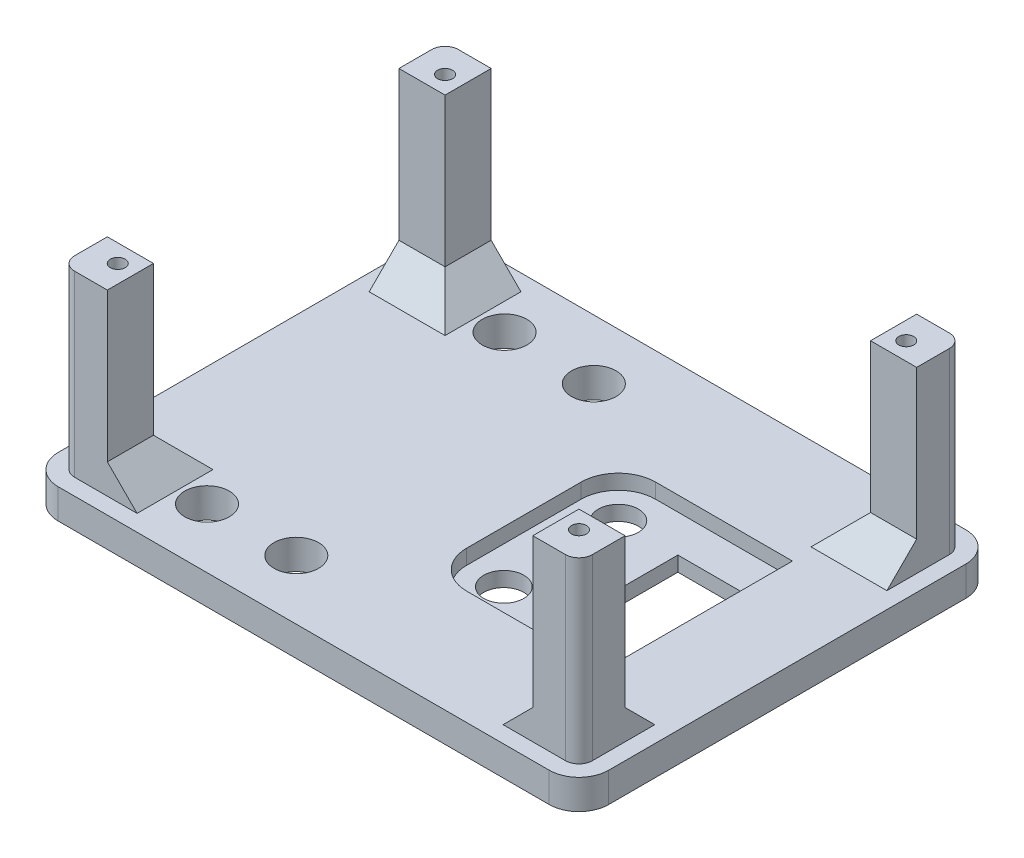
SolidWorks part; units mm, degrees
ref_plane "Front Plane" through (0, 0, 0) normal (0, 0, 1) x (1, 0, 0)
ref_plane "Top Plane" through (0, 0, 0) normal (0, 1, 0) x (1, 0, 0)
ref_plane "Right Plane" through (0, 0, 0) normal (1, 0, 0) x (0, 0, -1)
sketch "Sketch1" plane through (0, 0, 0) normal (0, 1, 0) x (1, 0, 0)
  line L1 (0, 0) -> (93.98, 0)
  line L2 (0, 0) -> (0, 71.12)
  line L3 (0, 71.12) -> (93.98, 71.12)
  line L4 (93.98, 0) -> (93.98, 71.12)
  dimension "D1" = 93.98
  dimension "D2" = 71.12
extrude "Boss-Extrude1" add sketch "Sketch1" along normal blind 5.08
sketch "Sketch2" plane through (0, 5.08, 0) normal (0, 1, 0) x (1, 0, 0)
  line L0 (46.99, 71.12) -> (46.99, 0) construction
  line L1 (2.794, 68.326) -> (10.668, 68.326)
  line L2 (2.794, 68.326) -> (2.794, 60.452)
  line L3 (2.794, 60.452) -> (10.668, 60.452)
  line L4 (10.668, 68.326) -> (10.668, 60.452)
  line L17 (93.98, 71.12) -> (0, 71.12) construction
  line L18 (0, 0) -> (93.98, 0) construction
  line L19 (0, 35.56) -> (93.98, 35.56) construction
  line L20 (0, 71.12) -> (0, 0) construction
  line L21 (93.98, 0) -> (93.98, 71.12) construction
  line L22 (83.312, 68.326) -> (83.312, 60.452)
  line L23 (91.186, 60.452) -> (83.312, 60.452)
  line L24 (91.186, 68.326) -> (91.186, 60.452)
  line L25 (91.186, 68.326) -> (83.312, 68.326)
  line L26 (91.186, 2.794) -> (83.312, 2.794)
  line L27 (91.186, 2.794) -> (91.186, 10.668)
  line L28 (91.186, 10.668) -> (83.312, 10.668)
  line L29 (83.312, 2.794) -> (83.312, 10.668)
  line L30 (10.668, 2.794) -> (10.668, 10.668)
  line L31 (2.794, 10.668) -> (10.668, 10.668)
  line L32 (2.794, 2.794) -> (2.794, 10.668)
  line L33 (2.794, 2.794) -> (10.668, 2.794)
  dimension "D1" = 7.874
  dimension "D2" = 7.874
  dimension "D3" = 2.794
  dimension "D4" = 2.794
fillet "Fillet4" radius 5.08 4 edges at (0, 2.54, -71.12) (93.98, 2.54, -71.12) (93.98, 2.54, 0) (0, 2.54, 0)
sketch "Sketch7" plane through (0, 5.08, 0) normal (0, 1, 0) x (1, 0, 0)
  line L0 (65.532, 35.56) -> (78.74, 35.56) construction
  line L1 (65.532, 45.339) -> (78.74, 45.339)
  line L2 (65.532, 45.339) -> (65.532, 25.781)
  line L3 (65.532, 25.781) -> (78.74, 25.781)
  line L4 (78.74, 45.339) -> (78.74, 25.781)
  circle A0 centre (55.372, 45.339) radius 3.429
  circle A1 centre (55.372, 25.781) radius 3.429
  dimension "D1" = 6.858
  dimension "D2" = 6.858
  dimension "D3" = 19.558
  dimension "D4" = 13.208
  dimension "D5" = 10.16
  dimension "D6" = 30.48
  dimension "D7" = 15.24
extrude "Cut-Extrude5" cut sketch "Sketch7" against normal up to next
sketch "Sketch8" plane through (0, 5.08, 0) normal (0, 1, 0) x (1, 0, 0)
  line L0 (5.08, 0) -> (88.9, 0) construction
  line L3 (0, 35.56) -> (93.98, 35.56) construction
  line L4 (0, 66.04) -> (0, 5.08) construction
  line L5 (93.98, 5.08) -> (93.98, 66.04) construction
  circle A2 centre (20.32, 10.16) radius 3.81
  circle A3 centre (35.56, 10.16) radius 3.81
  circle A4 centre (35.56, 60.96) radius 3.81
  circle A5 centre (20.32, 60.96) radius 3.81
  dimension "D1" = 15.24
  dimension "D2" = 7.62
  dimension "D4" = 7.62
  dimension "D3" = 10.16
  dimension "D5" = 15.24
sketch "Sketch9" plane through (0, 5.08, 0) normal (0, 1, 0) x (1, 0, 0)
  line L0 (55.372, 45.339) -> (55.372, 25.781) construction
  line L2 (49.022, 45.339) -> (49.022, 25.781)
  line L4 (65.532, 51.689) -> (78.74, 51.689)
  line L6 (65.532, 19.431) -> (78.74, 19.431)
  line L7 (78.74, 51.689) -> (78.74, 19.431)
  line L10 (78.74, 25.781) -> (78.74, 45.339) construction
  line L11 (55.372, 19.431) -> (65.532, 19.431)
  line L12 (55.372, 51.689) -> (65.532, 51.689)
  arc A0 (55.372, 51.689) -> (49.022, 45.339) centre (55.372, 45.339) ccw
  arc A1 (49.022, 25.781) -> (55.372, 19.431) centre (55.372, 25.781) ccw
  point P4 (55.372, 35.56)
  dimension "D2" = 6.35
  dimension "D3" = 6.35
extrude "Cut-Extrude7" cut sketch "Sketch9" against normal blind 2.54
extrude "Cut-Extrude8" cut sketch "Sketch8" against normal up to next
extrude "Boss-Extrude3" add sketch "Sketch2" along normal blind 30.48
sketch "Sketch10" plane through (0, 35.56, 0) normal (0, 1, 0) x (1, 0, 0)
  line L0 (46.99, 71.12) -> (46.99, 0) construction
  line L1 (88.9, 71.12) -> (5.08, 71.12) construction
  line L2 (5.08, 0) -> (88.9, 0) construction
  line L3 (0, 35.56) -> (93.98, 35.56) construction
  line L4 (0, 66.04) -> (0, 5.08) construction
  line L5 (93.98, 5.08) -> (93.98, 66.04) construction
  circle A0 centre (7.62, 63.5) radius 1.27
  circle A1 centre (86.36, 63.5) radius 1.27
  circle A2 centre (86.36, 7.62) radius 1.27
  circle A3 centre (7.62, 7.62) radius 1.27
  dimension "D1" = 7.62
  dimension "D3" = 2.54
  dimension "D2" = 7.62
extrude "Cut-Extrude9" cut sketch "Sketch10" against normal blind 12.7
fillet "Fillet5" radius 2.286 4 edges at (91.186, 20.32, -68.326) (91.186, 20.32, -2.794) (2.794, 20.32, -2.794) (2.794, 20.32, -68.326)
chamfer "Chamfer4" distance 5.08 angle 45 8 edges at (87.249, 5.08, -10.668) (83.312, 5.08, -6.731) (87.249, 5.08, -60.452) (83.312, 5.08, -64.389) (10.668, 5.08, -6.731) (6.731, 5.08, -10.668) (10.668, 5.08, -64.389) (6.731, 5.08, -60.452)
